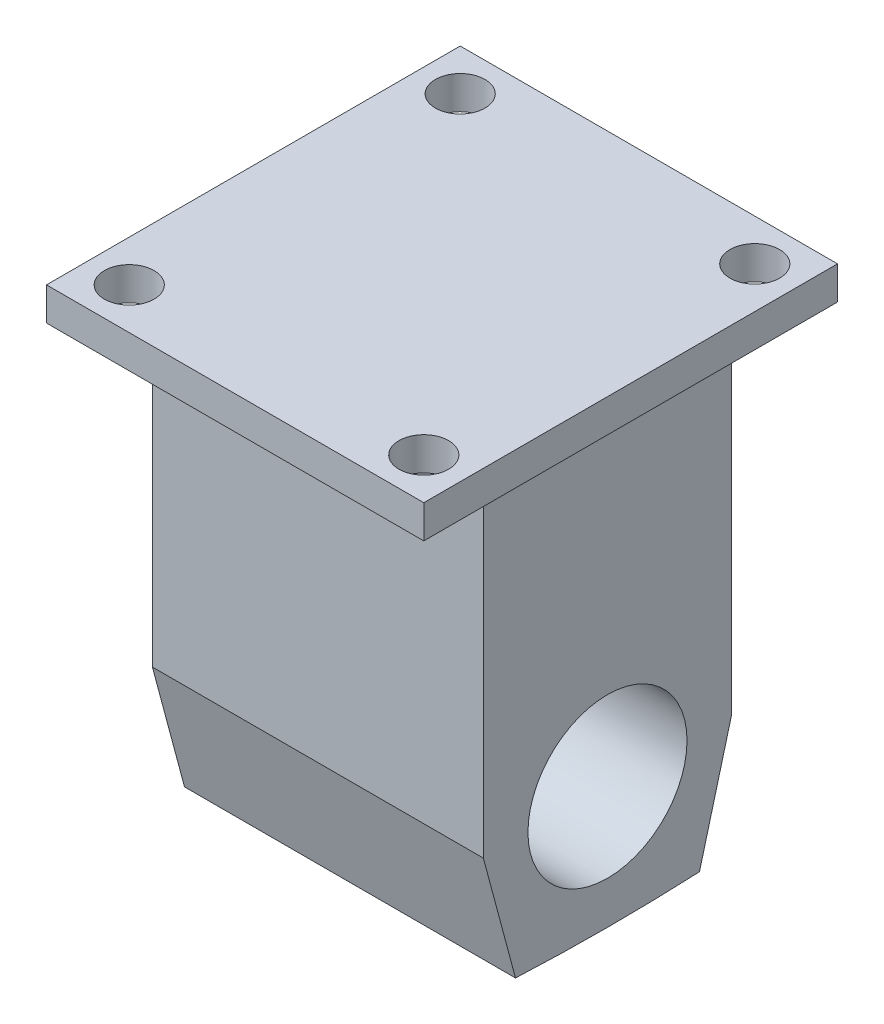
SolidWorks part; units mm, degrees
material "ABS"
ref_plane "Front Plane" through (0, 0, 0) normal (0, 0, 1) x (1, 0, 0)
ref_plane "Top Plane" through (0, 0, 0) normal (0, 1, 0) x (1, 0, 0)
ref_plane "Right Plane" through (0, 0, 0) normal (1, 0, 0) x (0, 0, -1)
sketch "Sketch1" plane through (0, 0, 0) normal (0, 1, 0) x (1, 0, 0)
  line L1 (-25.4, -19.05) -> (25.4, -19.05)
  line L2 (-25.4, -19.05) -> (-25.4, 19.05)
  line L3 (-25.4, 19.05) -> (25.4, 19.05)
  line L4 (25.4, -19.05) -> (25.4, 19.05)
  line L5 (-25.4, -19.05) -> (25.4, 19.05) construction
  line L6 (-25.4, 19.05) -> (25.4, -19.05) construction
  point P0 (0, 0)
extrude "Boss-Extrude1" add sketch "Sketch1" along normal blind 50.292
sketch "Sketch2" plane through (25.4, 0, 0) normal (1, 0, 0) x (0, 0, -1)
  line L0 (-19.05, 0) -> (-14.1195, -18.4009)
  line L1 (19.05, 0) -> (14.1195, -18.4009)
  line L2 (-19.05, 0) -> (19.05, 0)
  line L3 (-19.05, 0) -> (19.05, 0) construction
  arc A1 (14.1195, -18.4009) -> (-14.1195, -18.4009) centre (0, 281.2546) cw
  dimension "D1" = 19.05
  dimension "D2" = 19.05
  dimension "D3" = 75
  dimension "D4" = 75
extrude "Boss-Extrude2" add sketch "Sketch2" against normal up to vertex (50.8 mm away) contours L0 A1 L1 L2 up to point (-25.4, 0, -19.05)
sketch "Sketch3" plane through (25.4, 0, 0) normal (1, 0, 0) x (0, 0, -1)
  circle A0 centre (0, 0) radius 12.2085
extrude "Cut-Extrude1" cut sketch "Sketch3" against normal blind 127 contours A0
sketch "Sketch4" plane through (0, 50.292, 0) normal (0, 1, 0) x (1, 0, 0)
  line L1 (28.956, -31.75) -> (-28.956, -31.75)
  line L2 (28.956, -31.75) -> (28.956, 31.75)
  line L3 (28.956, 31.75) -> (-28.956, 31.75)
  line L4 (-28.956, -31.75) -> (-28.956, 31.75)
  line L5 (28.956, -31.75) -> (-28.956, 31.75) construction
  line L6 (28.956, 31.75) -> (-28.956, -31.75) construction
  point P0 (0, 0)
extrude "Boss-Extrude3" add sketch "Sketch4" along normal blind 5.08
sketch "Sketch5" plane through (0, 55.372, 0) normal (0, 1, 0) x (1, 0, 0)
  line L0 (0, -31.75) -> (0, 31.75) construction
  line L1 (28.956, 31.75) -> (-28.956, 31.75) construction
  line L2 (-28.956, 0) -> (28.956, 0) construction
  line L3 (28.956, -31.75) -> (28.956, 31.75) construction
  line L4 (-22.606, -31.75) -> (-22.606, 31.75) construction
  line L5 (-28.956, 25.4) -> (28.956, 25.4) construction
  line L6 (-28.956, 31.75) -> (-28.956, -31.75) construction
  circle A0 centre (-22.606, 25.4) radius 3.81
  circle A1 centre (-22.606, -25.4) radius 3.81
  circle A2 centre (22.606, 25.4) radius 3.81
  circle A3 centre (22.606, -25.4) radius 3.81
  point P6 (0, 0)
  point P12 (0, 0)
  point P15 (-22.606, 0)
  point P18 (0, 25.4)
  point P20 (-22.606, 25.4)
  dimension "D1" = 6.35
  dimension "D2" = 6.35
  dimension "D3" = 0
extrude "Cut-Extrude2" cut sketch "Sketch5" against normal blind 5.08
